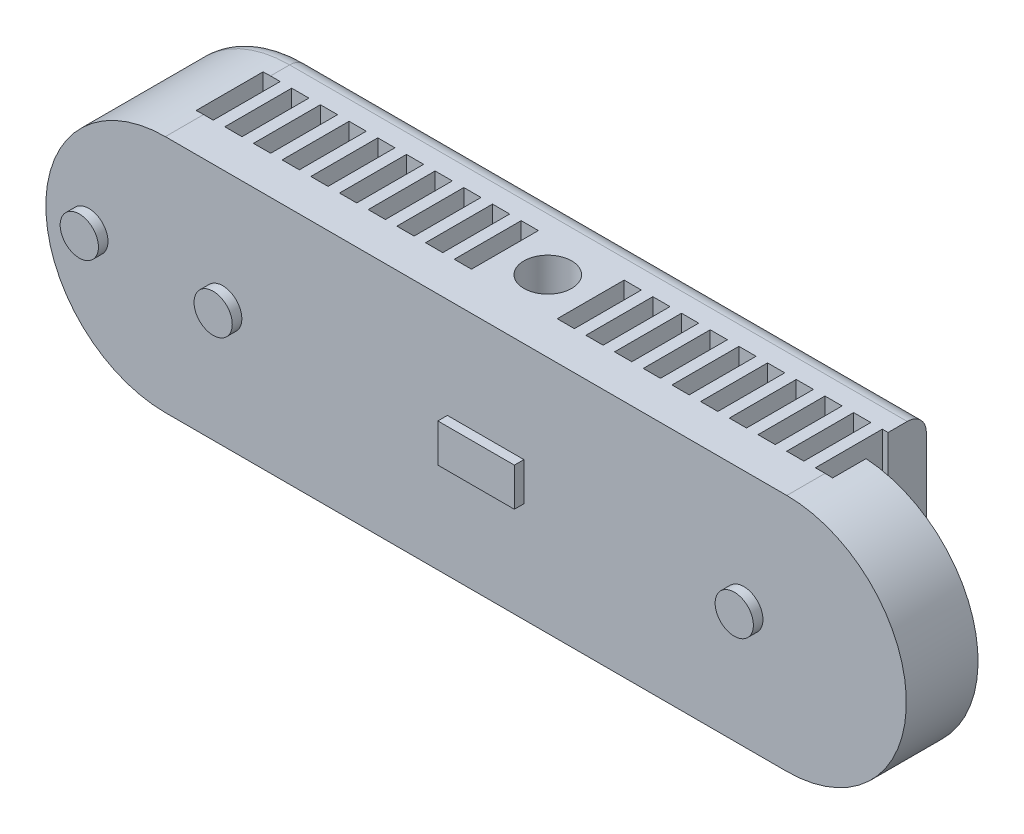
SolidWorks part; units mm, degrees
ref_plane "前视基准面" through (0, 0, 0) normal (0, 0, 1) x (1, 0, 0)
ref_plane "上视基准面" through (0, 0, 0) normal (0, 1, 0) x (1, 0, 0)
ref_plane "右视基准面" through (0, 0, 0) normal (1, 0, 0) x (0, 0, -1)
sketch "草图1" plane through (0, 0, 0) normal (0, 0, 1) x (1, 0, 0)
  line L1 (45, -12.5) -> (-45, -12.5)
  line L2 (45, -12.5) -> (45, 12.5)
  line L3 (45, 12.5) -> (-45, 12.5)
  line L4 (-45, -12.5) -> (-45, 12.5)
  line L5 (45, -12.5) -> (-45, 12.5) construction
  line L6 (45, 12.5) -> (-45, -12.5) construction
  point P0 (0, 0)
  dimension "D1" = 25
  dimension "D2" = 90
extrude "凸台-拉伸1" add sketch "草图1" along normal blind 15
sketch "草图2" plane through (0, 0, 15) normal (0, 0, 1) x (1, 0, 0)
  line L0 (45, 12.5) -> (-45, 12.5) construction
  line L1 (-45, -12.5) -> (45, -12.5) construction
  line L2 (-45, 12.5) -> (-45, -12.5) construction
  line L3 (45, -12.5) -> (45, 12.5) construction
  line L4 (-32.5, 12.5) -> (-61.4644, 12.5)
  line L5 (-61.4644, 12.5) -> (-61.4644, -12.5)
  line L6 (-61.4644, -12.5) -> (-32.5, -12.5)
  line L7 (32.5, 12.5) -> (60.8826, 12.5)
  line L8 (60.8826, 12.5) -> (60.8826, -12.5)
  line L9 (60.8826, -12.5) -> (32.5, -12.5)
  arc A0 (-32.5, 12.5) -> (-32.5, -12.5) centre (-32.5, 0) ccw
  arc A1 (32.5, -12.5) -> (32.5, 12.5) centre (32.5, 0) ccw
extrude "切除-拉伸1" cut sketch "草图2" against normal blind 15
sketch "草图3" plane through (0, 12.5, 0) normal (0, 1, 0) x (1, 0, 0)
  line L0 (32.5, 0) -> (-32.5, 0) construction
  circle A0 centre (0, -7.5) radius 2.5
  dimension "D1" = 5
  dimension "D2" = 7.5
extrude "切除-拉伸2" cut sketch "草图3" against normal blind 15
cosmetic thread "装饰螺纹线1" parameters "D2"=6
sketch "草图4" plane through (0, 12.5, 0) normal (0, 1, 0) x (1, 0, 0)
  line L0 (-7.4846, -11) -> (-7.4846, -4)
  line L1 (-4.4846, -11) -> (-6.2846, -11)
  line L2 (-4.4846, -11) -> (-4.4846, -4)
  line L3 (-4.4846, -4) -> (-6.2846, -4)
  line L4 (-6.2846, -11) -> (-6.2846, -4)
  line L5 (-4.4846, -11) -> (-6.2846, -4) construction
  line L6 (-4.4846, -4) -> (-6.2846, -11) construction
  line L7 (-7.4846, -11) -> (-9.2846, -11)
  line L8 (-9.2846, -11) -> (-9.2846, -4)
  line L9 (-7.4846, -4) -> (-9.2846, -4)
  line L10 (-10.4846, -11) -> (-10.4846, -4)
  line L11 (-10.4846, -11) -> (-12.2846, -11)
  line L12 (-12.2846, -11) -> (-12.2846, -4)
  line L13 (-10.4846, -4) -> (-12.2846, -4)
  line L14 (-13.4846, -11) -> (-13.4846, -4)
  line L15 (-13.4846, -11) -> (-15.2846, -11)
  line L16 (-15.2846, -11) -> (-15.2846, -4)
  line L17 (-13.4846, -4) -> (-15.2846, -4)
  line L18 (-16.4846, -11) -> (-16.4846, -4)
  line L19 (-16.4846, -11) -> (-18.2846, -11)
  line L20 (-18.2846, -11) -> (-18.2846, -4)
  line L21 (-16.4846, -4) -> (-18.2846, -4)
  line L22 (-19.4846, -11) -> (-19.4846, -4)
  line L23 (-19.4846, -11) -> (-21.2846, -11)
  line L24 (-21.2846, -11) -> (-21.2846, -4)
  line L25 (-19.4846, -4) -> (-21.2846, -4)
  line L26 (-22.4846, -11) -> (-22.4846, -4)
  line L27 (-22.4846, -11) -> (-24.2846, -11)
  line L28 (-24.2846, -11) -> (-24.2846, -4)
  line L29 (-22.4846, -4) -> (-24.2846, -4)
  line L30 (-25.4846, -11) -> (-25.4846, -4)
  line L31 (-25.4846, -11) -> (-27.2846, -11)
  line L32 (-27.2846, -11) -> (-27.2846, -4)
  line L33 (-25.4846, -4) -> (-27.2846, -4)
  line L34 (-28.4846, -11) -> (-28.4846, -4)
  line L35 (-28.4846, -11) -> (-30.2846, -11)
  line L36 (-30.2846, -11) -> (-30.2846, -4)
  line L37 (-28.4846, -4) -> (-30.2846, -4)
  line L38 (-31.4846, -11) -> (-31.4846, -4)
  line L39 (-31.4846, -11) -> (-33.2846, -11)
  line L40 (-33.2846, -11) -> (-33.2846, -4)
  line L41 (-31.4846, -4) -> (-33.2846, -4)
  point P0 (-5.3846, -7.5)
  dimension "D1" = 7
  dimension "D2" = 1.8
  dimension "D3" = 10
extrude "切除-拉伸3" cut sketch "草图4" against normal blind 5
mirror "镜向1" about plane through (0, 0, 0) normal (1, 0, 0) of "切除-拉伸3"
sketch "草图5" plane through (0, 0, 0) normal (0, 0, -1) x (-1, 0, 0)
  circle A0 centre (-22.5, 0) radius 1.65
  circle A1 centre (22.5, 0) radius 1.65
  dimension "D1" = 3.3
  dimension "D2" = 3.3
  dimension "D3" = 22.5
  dimension "D4" = 22.5
extrude "切除-拉伸4" cut sketch "草图5" against normal blind 5
cosmetic thread "装饰螺纹线2" parameters "D2"=4
cosmetic thread "装饰螺纹线3" parameters "D2"=4
sketch "草图6" plane through (0, -12.5, 0) normal (0, -1, 0) x (1, 0, 0)
  line L0 (-32.5, 0) -> (32.5, 0) construction
  line L1 (10, 1.25) -> (-10, 1.25)
  line L2 (10, 1.25) -> (10, 3.75)
  line L3 (10, 3.75) -> (-10, 3.75)
  line L4 (-10, 1.25) -> (-10, 3.75)
  line L5 (10, 1.25) -> (-10, 3.75) construction
  line L6 (10, 3.75) -> (-10, 1.25) construction
  point P0 (0, 2.5)
  dimension "D1" = 2.5
  dimension "D2" = 20
  dimension "D3" = 2.5
extrude "切除-拉伸5" cut sketch "草图6" against normal blind 5
sketch "草图7" plane through (0, 0, 0) normal (0, 0, -1) x (-1, 0, 0)
  line L0 (-32.5, 9) -> (-32.5, -9)
  arc A0 (-32.5, 9) -> (-32.5, -9) centre (-32.5, 0) ccw
extrude "切除-拉伸7" cut sketch "草图7" against normal blind 7.5
sketch "草图8" plane through (32.5, 0, 0) normal (1, 0, 0) x (0, 0, -1)
  line L2 (-1.9178, -4) -> (-1.9178, 4)
  line L4 (-3.9178, -4) -> (-3.9178, 4)
  line L5 (-1.9178, -4) -> (-3.9178, 4) construction
  line L6 (-1.9178, 4) -> (-3.9178, -4) construction
  arc A0 (-1.9178, 4) -> (-3.9178, 4) centre (-2.9178, 4) ccw
  arc A1 (-3.9178, -4) -> (-1.9178, -4) centre (-2.9178, -4) ccw
  point P0 (-2.9178, 0)
  dimension "D1" = 1
  dimension "D2" = 1
  dimension "D3" = 8
extrude "切除-拉伸8" cut sketch "草图8" against normal blind 7.5
sketch "草图9" plane through (0, 0, 15) normal (0, 0, 1) x (1, 0, 0)
  line L1 (5, -2) -> (-3, -2)
  line L2 (5, -2) -> (5, 2)
  line L3 (5, 2) -> (-3, 2)
  line L4 (-3, -2) -> (-3, 2)
  line L5 (5, -2) -> (-3, 2) construction
  line L6 (5, 2) -> (-3, -2) construction
  circle A0 centre (28, 0) radius 2
  circle A1 centre (-26.5, 0) radius 2
  circle A2 centre (-40.5, 0) radius 2
  arc A4 (32.5, -12.5) -> (32.5, 12.5) centre (32.5, 0) ccw construction
  point P6 (1, 0)
  point P14 (45, 0)
  dimension "D1" = 4
  dimension "D2" = 4
  dimension "D3" = 4
  dimension "D7" = 27
  dimension "D9" = 14
  dimension "D6" = 17
  dimension "D4" = 4
  dimension "D5" = 8
  dimension "D8" = 27.5
extrude "凸台-拉伸2" add sketch "草图9" along normal blind 1
fillet "圆角1" radius 2 4 edges at (0, -12.5, 0) (-45, 0, 0) (0, 12.5, 0) (45, 0, 0)
sketch "草图11" plane through (0, 0, 15) normal (0, 0, 1) x (1, 0, 0)
  line L0 (43.4659, 6) -> (-43.4659, 6) construction
  arc A0 (-32.5, 12.5) -> (-32.5, -12.5) centre (-32.5, 0) ccw construction
  arc A1 (32.5, -12.5) -> (32.5, 12.5) centre (32.5, 0) ccw construction
  text T0 "我是个有深度的摄像头" font "华文隶书" height 2
  dimension "D1" = 6
extrude "切除-拉伸9" [suppressed] cut sketch "草图11" against normal blind 1
sketch "草图12" plane through (0, 0, 16) normal (0, 0, 1) x (1, 0, 0)
  line L1 (29.4142, -1.4142) -> (26.5858, -1.4142)
  line L2 (29.4142, -1.4142) -> (29.4142, 1.4142)
  line L3 (29.4142, 1.4142) -> (26.5858, 1.4142)
  line L4 (26.5858, -1.4142) -> (26.5858, 1.4142)
  line L5 (29.4142, -1.4142) -> (26.5858, 1.4142) construction
  line L6 (29.4142, 1.4142) -> (26.5858, -1.4142) construction
  circle A0 centre (28, 0) radius 2 construction
  point P0 (28, 0)
ref_plane "基准面1" through (0, 0, 156) normal (0, 0, 1) x (1, 0, 0)
sketch "草图13" plane through (0, 0, 156) normal (0, 0, 1) x (1, 0, 0)
  line L1 (127.1022, -99.1022) -> (-71.1022, -99.1022)
  line L2 (127.1022, -99.1022) -> (127.1022, 99.1022)
  line L3 (127.1022, 99.1022) -> (-71.1022, 99.1022)
  line L4 (-71.1022, -99.1022) -> (-71.1022, 99.1022)
  line L5 (127.1022, -99.1022) -> (-71.1022, 99.1022) construction
  line L6 (127.1022, 99.1022) -> (-71.1022, -99.1022) construction
  point P0 (28, 0)
sketch "草图14" plane through (0, 0, 0) normal (1, 0, 0) x (0, 0, -1)
  line L0 (-156, 99.1022) -> (-16, 1.0731)
  line L1 (-156, -99.1022) -> (-156, 99.1022) construction
  line L2 (-16, -1.4142) -> (-16, 1.4142) construction
  line L3 (-16, 1.4142) -> (-16, -1.4142) construction
  line L4 (-16, 1.0731) -> (-156, 1.0731)
  dimension "D1" = 35
loft "放样1" [suppressed] add profiles "草图12", "草图13"
sketch "草图15" plane through (0, 0, 0) normal (0, 0, -1) x (-1, 0, 0)
  line L1 (-32.0901, 19.8503) -> (-49.2945, 19.8503)
  line L2 (-32.0901, 19.8503) -> (-32.0901, -15.5706)
  line L3 (-32.0901, -15.5706) -> (-49.2945, -15.5706)
  line L4 (-49.2945, 19.8503) -> (-49.2945, -15.5706)
extrude "切除-拉伸10" cut sketch "草图15" against normal up to surface (7.5 mm away) up to face at (35.0421, 3.6475, 7.5)
